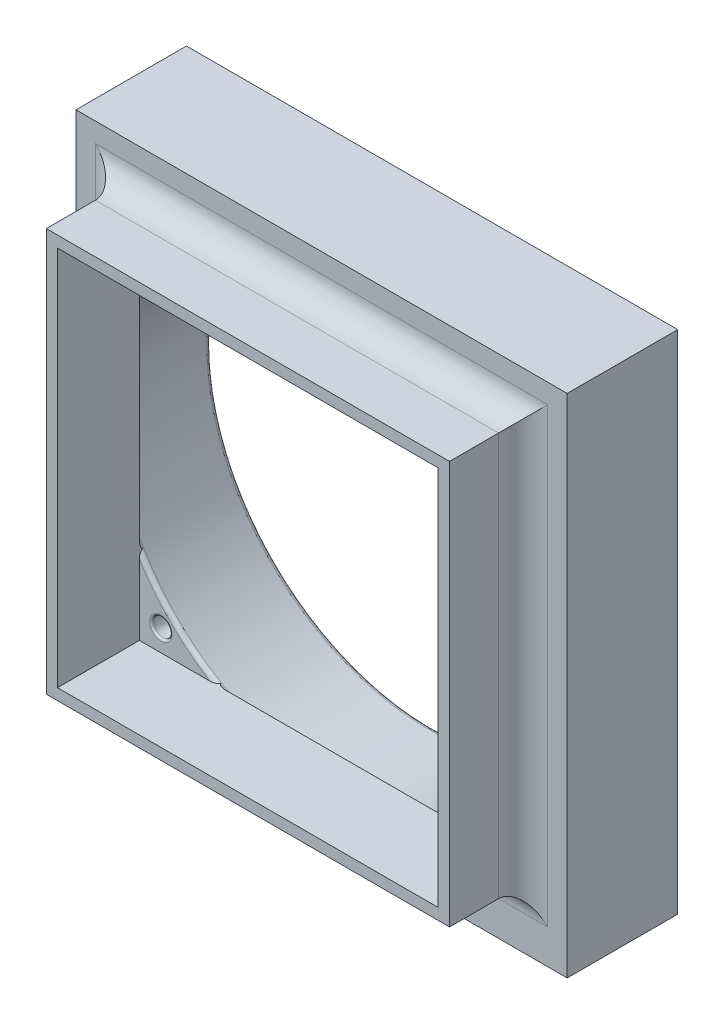
SolidWorks part; units mm, degrees
ref_plane "Ebene vorne" through (0, 0, 0) normal (0, 0, 1) x (1, 0, 0)
ref_plane "Ebene oben" through (0, 0, 0) normal (0, 1, 0) x (1, 0, 0)
ref_plane "Ebene rechts" through (0, 0, 0) normal (1, 0, 0) x (0, 0, -1)
sketch "Skizze1" plane through (0, 0, 0) normal (0, 0, 1) x (1, 0, 0)
  line L9 (-45.25, -45.25) -> (45.25, -45.25)
  line L10 (-45.25, -45.25) -> (-45.25, 45.25)
  line L11 (-45.25, 45.25) -> (45.25, 45.25)
  line L12 (45.25, -45.25) -> (45.25, 45.25)
  line L13 (-49.25, 49.25) -> (49.25, 49.25)
  line L14 (-49.25, 49.25) -> (-49.25, -49.25)
  line L15 (-49.25, -49.25) -> (49.25, -49.25)
  line L16 (49.25, 49.25) -> (49.25, -49.25)
  arc A0 (-21.2706, -45.25) -> (-45.25, -21.2706) centre (0, 0) cw
  arc A1 (-45.25, 21.2706) -> (-21.2706, 45.25) centre (0, 0) cw
  arc A2 (21.2706, 45.25) -> (45.25, 21.2706) centre (0, 0) cw
  arc A3 (21.2706, -45.25) -> (45.25, -21.2706) centre (0, 0) ccw
  dimension "D1" = 45.25
  dimension "D2" = 45.25
  dimension "D3" = 90.5
  dimension "D4" = 90.5
  dimension "D5" = 50
  dimension "D6" = 50
  dimension "D7" = 50
  dimension "D8" = 50
  dimension "D9" = 4
  dimension "D10" = 4
  dimension "D11" = 4
  dimension "D12" = 4
extrude "Aufsatz-Linear austragen2" add sketch "Skizze1" along normal blind 20 contours L10 A1 L11 | L16 L13 L14 L15 L12 L9 L10 L11 | L11 A2 L12 | A3 L9 L12 | L9 A0 L10
sketch "Skizze11" plane through (0, 0, 20) normal (0, 0, 1) x (1, 0, 0)
  line L0 (-49.25, 49.25) -> (49.25, 49.25) construction
  line L1 (-46.5, 46.5) -> (46.5, 46.5)
  line L2 (-46.5, 46.5) -> (-46.5, -46.5)
  line L3 (-46.5, -46.5) -> (46.5, -46.5)
  line L4 (46.5, 46.5) -> (46.5, -46.5)
  line L5 (-49.25, 49.25) -> (-49.25, -49.25) construction
  dimension "D1" = 93
  dimension "D2" = 93
  dimension "D3" = 2.75
  dimension "D4" = 2.75
extrude "Schnitt-Linear austragen2" cut sketch "Skizze11" against normal blind 15
sketch "Skizze12" plane through (0, 0, 0) normal (0, 0, -1) x (-1, 0, 0)
  line L1 (-60, -63.6684) -> (60, -63.6684)
  line L2 (-60, -63.6684) -> (-60, 60)
  line L3 (-60, 60) -> (60, 60)
  line L4 (60, -63.6684) -> (60, 60)
  circle A0 centre (0, 0) radius 54
  dimension "D2" = 108
  dimension "D1" = 120
  dimension "D3" = 60
  dimension "D4" = 60
  dimension "D5" = 120
extrude "Aufsatz-Linear austragen6" add sketch "Skizze12" along normal blind 25
sketch "Skizze15" plane through (0, 0, 0) normal (0, 0, 1) x (1, 0, 0)
  line L1 (49.25, -49.25) -> (-49.25, -49.25)
  line L2 (49.25, -49.25) -> (49.25, 49.25)
  line L3 (49.25, 49.25) -> (-49.25, 49.25)
  line L4 (-49.25, -49.25) -> (-49.25, 49.25)
  line L5 (-60, 60) -> (60, 60)
  line L6 (-60, 60) -> (-60, -63.6684)
  line L7 (-60, -63.6684) -> (60, -63.6684)
  line L8 (60, 60) -> (60, -63.6684)
extrude "Aufsatz-Linear austragen8" add sketch "Skizze15" along normal blind 2
sketch "Skizze16" plane through (0, 0, 5) normal (0, 0, 1) x (1, 0, 0)
  line L0 (46.5, 46.5) -> (-46.5, 46.5) construction
  line L1 (-46.5, -46.5) -> (46.5, -46.5)
  line L2 (-46.5, -46.5) -> (-46.5, 46.5)
  line L3 (-46.5, 46.5) -> (46.5, 46.5)
  line L4 (46.5, -46.5) -> (46.5, 46.5)
extrude "Schnitt-Linear austragen3" cut sketch "Skizze16" against normal up to surface (5 mm away) up to face at (0, 0, 0)
sketch "Skizze17" plane through (0, 0, 0) normal (0, 0, 1) x (1, 0, 0)
  line L0 (46.5, -27.4545) -> (46.5, -46.5) construction
  line L1 (46.5, -46.5) -> (27.4545, -46.5) construction
  line L2 (27.4545, 46.5) -> (46.5, 46.5) construction
  line L3 (46.5, 46.5) -> (46.5, 27.4545) construction
  line L4 (-27.4545, -46.5) -> (-46.5, -46.5) construction
  line L5 (-46.5, -46.5) -> (-46.5, -27.4545) construction
  line L6 (-46.5, 27.4545) -> (-46.5, 46.5) construction
  line L7 (-46.5, 46.5) -> (-27.4545, 46.5) construction
  circle A0 centre (41.25, -41.25) radius 2.25
  circle A1 centre (-41.25, -41.25) radius 2.25
  circle A2 centre (-41.25, 41.25) radius 2.25
  circle A3 centre (41.25, 41.25) radius 2.25
  dimension "D1" = 4.5
  dimension "D4" = 4.5
  dimension "D5" = 4.5
  dimension "D6" = 4.5
  dimension "D2" = 5.25
  dimension "D3" = 5.25
  dimension "D7" = 5.25
  dimension "D8" = 5.25
  dimension "D9" = 5.25
  dimension "D10" = 5.25
  dimension "D11" = 5.25
  dimension "D12" = 5.25
extrude "Schnitt-Linear austragen4" cut sketch "Skizze17" against normal blind 6
fillet "Verrundung1" radius 0.5 4 edges at (-39, -41.25, 0) (-39, 41.25, 0) (43.5, 41.25, 0) (43.5, -41.25, 0)
fillet "Verrundung3" radius 1 1 edges at (0, -54, 0)
fillet "Verrundung5" radius 1 1 edges at (-54, 0, -25)
fillet "Verrundung7" radius 1 4 edges at (-38.1838, -38.1838, 0) (38.1838, -38.1838, 0) (38.1838, 38.1838, 0) (-38.1838, 38.1838, 0)
fillet "Verrundung8" radius 6 4 edges at (0, -49.25, 2) (-49.25, 0, 2) (0, 49.25, 2) (49.25, 0, 2)
